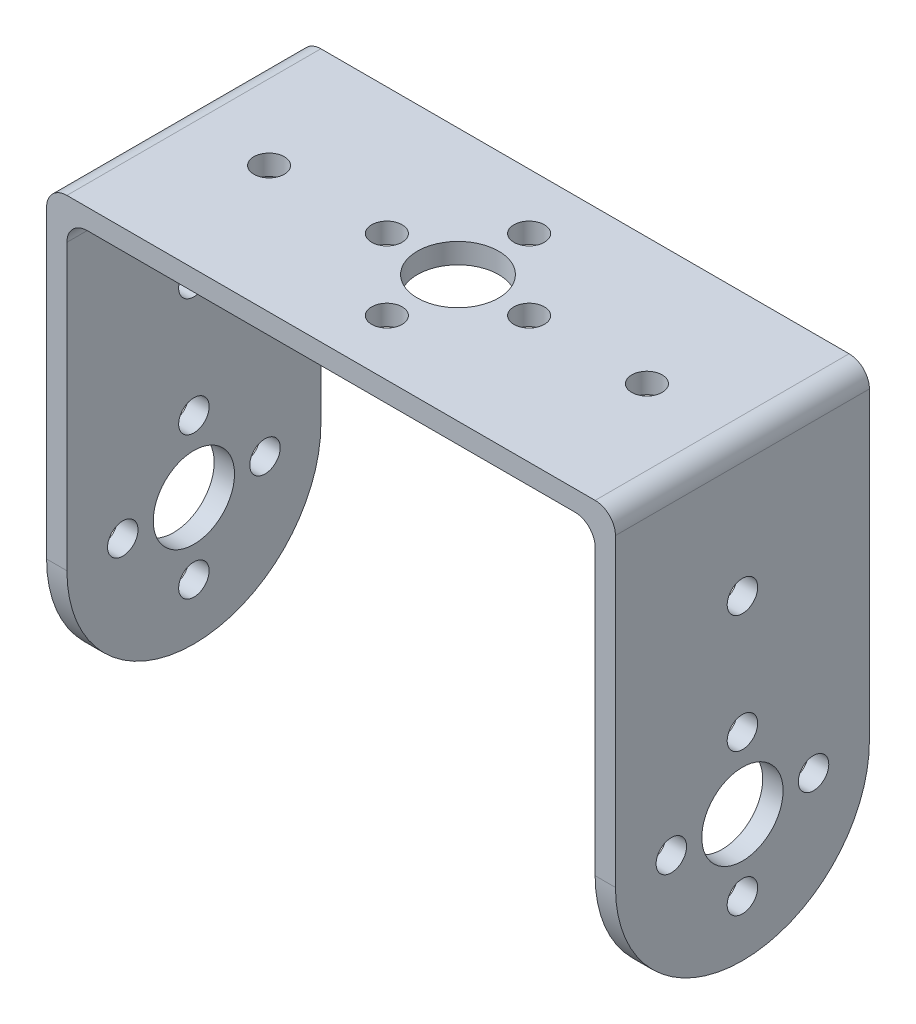
SolidWorks part; units mm, degrees
ref_plane "前视基准面" through (0, 0, 0) normal (0, 0, 1) x (1, 0, 0)
ref_plane "上视基准面" through (0, 0, 0) normal (0, 1, 0) x (1, 0, 0)
ref_plane "右视基准面" through (0, 0, 0) normal (1, 0, 0) x (0, 0, -1)
sketch "草图1" plane through (0, 0, 0) normal (0, 1, 0) x (1, 0, 0)
  line L0 (0, 0) -> (-52, 0)
  line L1 (-52, 0) -> (-52, 25)
  line L2 (-52, 25) -> (0, 25)
  line L3 (0, 25) -> (0, 0)
  circle A0 centre (-26, 12.5) radius 4
  circle A2 centre (-26, 5.5) radius 1.5
  circle A3 centre (-33, 12.5) radius 1.5
  circle A4 centre (-26, 19.5) radius 1.5
  circle A5 centre (-19, 12.5) radius 1.5
  circle A6 centre (-7.4, 12.5) radius 1.5
  circle A7 centre (-44.6, 12.5) radius 1.5
  point P19 (-26, 12.5)
  dimension "D1" = 4
extrude "凸台-拉伸1" add sketch "草图1" along normal blind 2
sketch "草图2" plane through (0, 2, 0) normal (0, 1, 0) x (1, 0, 0)
  line L0 (-52, 0) -> (-54, 0)
  line L1 (-54, 0) -> (-54, 25)
  line L2 (-54, 25) -> (-52, 25)
  line L3 (0, 0) -> (2, 0)
  line L4 (2, 0) -> (2, 25)
  line L5 (2, 25) -> (0, 25)
  line L6 (0, 25) -> (0, 0)
  line L7 (-52, 25) -> (-52, 0)
extrude "凸台-拉伸2" add sketch "草图2" against normal blind 44.5
fillet "圆角1" radius 12.5 2 edges at (-53, -42.5, -25) (-53, -42.5, 0)
fillet "圆角2" radius 12.5 2 edges at (1, -42.5, -25) (1, -42.5, 0)
sketch "草图3" plane through (2, 0, 0) normal (1, 0, 0) x (0, 0, -1)
  circle A0 centre (12.5, -30) radius 4
  circle A2 centre (12.5, -23) radius 1.5
  circle A3 centre (19.5, -30) radius 1.5
  circle A4 centre (12.5, -37) radius 1.5
  circle A5 centre (5.5, -30) radius 1.5
  circle A6 centre (12.5, -11.4) radius 1.5
  point P15 (12.5, -30)
  dimension "D1" = 4
extrude "切除-拉伸1" cut sketch "草图3" against normal blind 64.5
fillet "圆角5" radius 2 4 edges at (0, 0, -12.5) (-52, 0, -12.5) (-54, 2, -12.5) (2, 2, -12.5)
